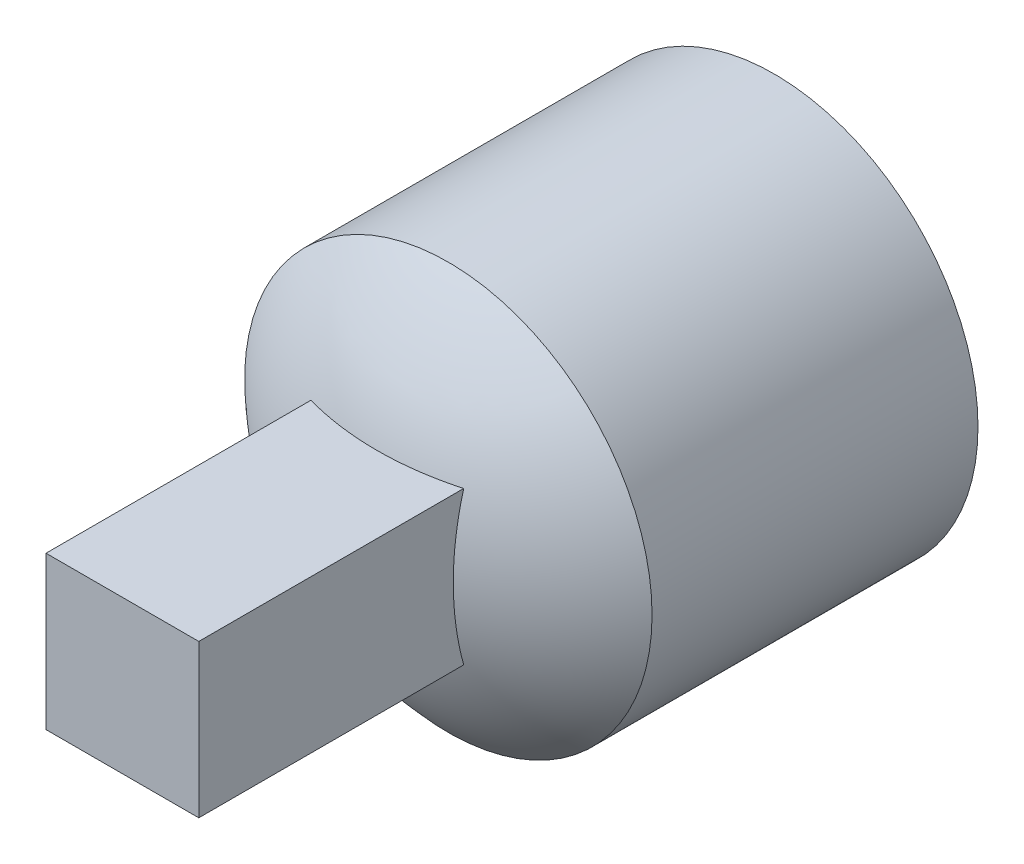
SolidWorks part; units mm, degrees
material "ASTM A36 Steel"
ref_plane "Front Plane" through (0, 0, 0) normal (0, 0, 1) x (1, 0, 0)
ref_plane "Top Plane" through (0, 0, 0) normal (0, 1, 0) x (1, 0, 0)
ref_plane "Right Plane" through (0, 0, 0) normal (1, 0, 0) x (0, 0, -1)
sketch "Sketch1" plane through (0, 0, 0) normal (0, 0, 1) x (1, 0, 0)
  circle A0 centre (0, 0) radius 6.35
  dimension "D1" = 12.7
extrude "Boss-Extrude1" add sketch "Sketch1" along normal blind 10.16
dome "Dome1" faces to dome 1 distance 2.54 reverse direction no elliptical dome no face at (6.35, 0, 10.16) parameters "D1"=2.54
ref_plane "Plane1" through (0, 0, 7.62) normal (0, 0, -1) x (-1, 0, 0)
sketch "Sketch3" plane through (0, 0, 7.62) normal (0, 0, -1) x (-1, 0, 0)
  line L1 (-1.905, -1.905) -> (1.905, -1.905)
  line L2 (-1.905, -1.905) -> (-1.905, 1.905)
  line L3 (-1.905, 1.905) -> (1.905, 1.905)
  line L4 (1.905, -1.905) -> (1.905, 1.905)
  line L5 (-1.905, -1.905) -> (1.905, 1.905) construction
  line L6 (-1.905, 1.905) -> (1.905, -1.905) construction
  point P0 (0, 0)
  dimension "D1" = 3.81
  dimension "D2" = 3.81
extrude "Cut-Extrude1" cut sketch "Sketch3" along normal blind 7.62
sketch "Sketch5" plane through (0, 0, 7.62) normal (0, 0, -1) x (-1, 0, 0)
  line L1 (-2.3813, -2.3813) -> (2.3812, -2.3813)
  line L2 (-2.3813, -2.3813) -> (-2.3813, 2.3813)
  line L3 (-2.3813, 2.3813) -> (2.3812, 2.3813)
  line L4 (2.3812, -2.3813) -> (2.3812, 2.3813)
  line L5 (-2.3813, -2.3813) -> (2.3812, 2.3813) construction
  line L6 (-2.3813, 2.3813) -> (2.3812, -2.3813) construction
  point P0 (0, 0)
  dimension "D1" = 4.7625
  dimension "D2" = 4.7625
extrude "Boss-Extrude2" add sketch "Sketch5" against normal blind 12.7
sketch "Sketch6" plane through (-1.905, 0, 0) normal (1, 0, 0) x (0, 0, -1)
  circle A0 centre (-3.9688, 0) radius 1.5875
  dimension "D1" = 3.175
extrude "Cut-Extrude2" cut sketch "Sketch6" against normal blind 12.7
